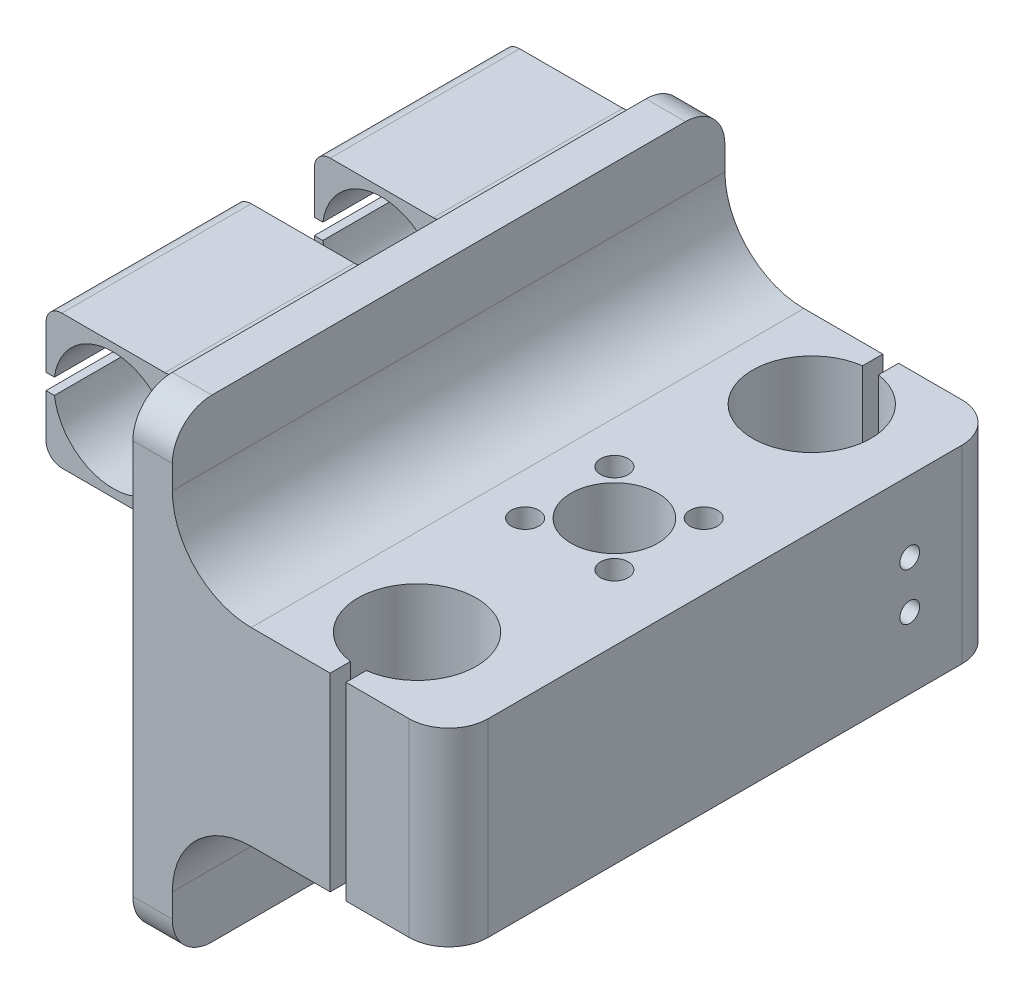
SolidWorks part; units mm, degrees
ref_plane "Plan de face" through (0, 0, 0) normal (0, 0, 1) x (1, 0, 0)
ref_plane "Plan de dessus" through (0, 0, 0) normal (0, 1, 0) x (1, 0, 0)
ref_plane "Plan de droite" through (0, 0, 0) normal (1, 0, 0) x (0, 0, -1)
sketch "Sketch1" plane through (0, 0, 0) normal (1, 0, 0) x (0, 0, -1)
  line L4 (-37.2098, 55.762) -> (32.7902, 55.762)
  line L7 (-37.2098, 55.762) -> (-37.2098, -4.238)
  line L8 (-37.2098, -4.238) -> (32.7902, -4.238)
  line L9 (32.7902, 55.762) -> (32.7902, -4.238)
  dimension "D1" = 70
  dimension "D2" = 60
extrude "Boss-Extrude3" add sketch "Sketch1" along normal blind 5
fillet "Fillet2" radius 5 4 edges at (2.5, -4.238, 37.2098) (2.5, -4.238, -32.7902) (2.5, 55.762, -32.7902) (2.5, 55.762, 37.2098)
sketch "Sketch4" plane through (5, 0, 0) normal (1, 0, 0) x (0, 0, -1)
  line L1 (-37.2098, 13.762) -> (32.7902, 13.762)
  line L2 (-37.2098, 13.762) -> (-37.2098, 37.762)
  line L3 (-37.2098, 37.762) -> (32.7902, 37.762)
  line L4 (32.7902, 13.762) -> (32.7902, 37.762)
  line L5 (32.7902, 0.762) -> (32.7902, 50.762) construction
  line L6 (-37.2098, 50.762) -> (-37.2098, 0.762) construction
  point P8 (32.7902, 25.762)
  point P9 (32.7902, 25.762)
  dimension "D1" = 24
extrude "Boss-Extrude5" add sketch "Sketch4" along normal blind 35
fillet "Fillet4" radius 5 2 edges at (40, 25.762, 37.2098) (40, 25.762, -32.7902)
sketch "Sketch5" plane through (0, 13.762, 0) normal (0, -1, 0) x (-1, 0, 0)
  line L0 (-47, -37.2098) -> (-47, 32.7902) construction
  line L1 (-35, -37.2098) -> (-5, -37.2098) construction
  line L2 (-35, 32.7902) -> (-5, 32.7902) construction
  line L4 (-5, -37.2098) -> (-5, 32.7902) construction
  line L5 (-47, -37.2098) -> (-5, 32.7902) construction
  line L6 (-47, 32.7902) -> (-5, -37.2098) construction
  line L7 (-20.3431, -2.2098) -> (-31.6569, -2.2098) construction
  line L8 (-31.6569, -7.8666) -> (-20.3431, -7.8666) construction
  line L9 (-31.6569, -7.8666) -> (-31.6569, 3.4471) construction
  line L10 (-31.6569, 3.4471) -> (-20.3431, 3.4471) construction
  line L11 (-20.3431, -7.8666) -> (-20.3431, 3.4471) construction
  line L12 (-31.6569, -7.8666) -> (-20.3431, 3.4471) construction
  line L13 (-31.6569, 3.4471) -> (-20.3431, -7.8666) construction
  line L14 (-26, -7.8666) -> (-26, 3.4471) construction
  line L15 (-27, 27.895) -> (-25, 27.895)
  line L16 (-27, 27.895) -> (-27, 37.3036)
  line L17 (-27, 37.3036) -> (-25, 37.3036)
  line L18 (-25, 27.895) -> (-25, 37.3036)
  line L19 (-27, -41.5182) -> (-25, -41.5182)
  line L20 (-27, -41.5182) -> (-27, -32.5795)
  line L21 (-27, -32.5795) -> (-25, -32.5795)
  line L22 (-25, -41.5182) -> (-25, -32.5795)
  circle A0 centre (-31.6569, 3.4471) radius 1.75
  circle A1 centre (-31.6569, -7.8666) radius 1.75
  circle A2 centre (-20.3431, -7.8666) radius 1.75
  circle A3 centre (-20.3431, 3.4471) radius 1.75
  circle A4 centre (-26, -2.2098) radius 5.5
  circle A5 centre (-26, 22.7902) radius 7.5
  circle A6 centre (-26, -27.2098) radius 7.5
  point P10 (-26, -2.2098)
  point P36 (-26, 27.895)
  point P37 (-26, -41.5182)
  line M32 (-35, -37.2098) -> (-5, -37.2098)
  line M34 (-5, 32.7902) -> (-35, 32.7902)
  dimension "D5" = 11
  dimension "D6" = 3.5
  dimension "D7" = 3.5
  dimension "D8" = 3.5
  dimension "D9" = 3.5
  dimension "D3" = 15
  dimension "D2" = 42
  dimension "D4" = 25
  dimension "D10" = 8
  dimension "D11" = 0
  dimension "D12" = 2
  dimension "D13" = 2
extrude "Cut-Extrude2" cut sketch "Sketch5" against normal through all both and the other way through all contours A6 | A5 | A1 | A0 | A3 | A2 | A4 | L18 A5 L16 L15 | A5 L18 L16 M34 | L18 L17 L16 M34 | A6 L22 L21 L20 | L22 A6 L20 M32 | L19 L22 L20 M32 region at (26, 13.762, -29.0816) region at (26, 13.762, -22.6166) region at (26, 13.762, -31.529) region at (26, 13.762, -35.0469) region at (26, 13.762, 39.364) region at (26, 13.762, 35.9486) region at (26, 13.762, 27.0528) region at (26, 13.762, 33.6336) region at (31.6569, 13.762, -3.4471) region at (31.6569, 13.762, 7.8666) region at (20.3431, 13.762, 7.8666) region at (20.3431, 13.762, -3.4471) region at (26, 13.762, 2.2098)
fillet "Fillet5" radius 10 2 edges at (5, 13.762, 2.2098) (5, 37.762, 2.2098)
sketch "Sketch6" plane through (0, 0, 0) normal (-1, 0, 0) x (0, 0, 1)
  line L0 (-9.7902, 14.262) -> (14.2098, 14.262)
  line L1 (-26.7902, 54.262) -> (-2.7902, 54.262)
  line L2 (-26.7902, 54.262) -> (-26.7902, 37.262)
  line L3 (-26.7902, 37.262) -> (-2.7902, 37.262)
  line L4 (-2.7902, 54.262) -> (-2.7902, 37.262)
  line L5 (-9.7902, 14.262) -> (-9.7902, -2.738)
  line L6 (-9.7902, -2.738) -> (14.2098, -2.738)
  line L7 (14.2098, 14.262) -> (14.2098, -2.738)
  line L8 (7.2098, 54.262) -> (31.2098, 54.262)
  line L9 (7.2098, 54.262) -> (7.2098, 37.262)
  line L10 (7.2098, 37.262) -> (31.2098, 37.262)
  line L11 (31.2098, 54.262) -> (31.2098, 37.262)
  line L12 (32.2098, -4.238) -> (-27.7902, -4.238) construction
  line L13 (-27.7902, 55.762) -> (32.2098, 55.762) construction
  point P16 (-9.7902, 5.762)
  point P17 (-26.7902, 45.762)
  point P18 (-2.7902, 45.762)
  point P19 (7.2098, 45.762)
  point P22 (2.2098, -2.738)
  point P25 (2.2098, -4.238)
  point P30 (2.2098, 55.762)
  dimension "D1" = 17
  dimension "D2" = 24
  dimension "D3" = 17
  dimension "D4" = 24
  dimension "D5" = 17
  dimension "D6" = 24
  dimension "D7" = 40
  dimension "D8" = 10
  dimension "D9" = 1.5
  dimension "D10" = 1.5
  dimension "D11" = 5
extrude "Boss-Extrude6" add sketch "Sketch6" along normal blind 17
sketch "Sketch7" plane through (0, 0, -26.7902) normal (0, 0, -1) x (-1, 0, 0)
  line L0 (17, 14.262) -> (0, 14.262) construction
  line L1 (17, 14.262) -> (17, -2.738) construction
  line L2 (17, 54.262) -> (0, 54.262) construction
  line L3 (17, 54.262) -> (17, 37.262) construction
  line L5 (14.7083, 46.762) -> (18.6764, 46.762)
  line L6 (14.7083, 46.762) -> (14.7083, 44.762)
  line L7 (14.7083, 44.762) -> (18.6764, 44.762)
  line L8 (18.6764, 46.762) -> (18.6764, 44.762)
  line L9 (14.795, 6.762) -> (19.3087, 6.762)
  line L10 (14.795, 6.762) -> (14.795, 4.762)
  line L11 (14.795, 4.762) -> (19.3087, 4.762)
  line L12 (19.3087, 6.762) -> (19.3087, 4.762)
  circle A0 centre (8.5, 45.762) radius 7.5
  circle A1 centre (8.5, 5.762) radius 7.5
  point P7 (8.5, 14.262)
  point P11 (17, 5.762)
  point P15 (8.5, 54.262)
  point P17 (14.7083, 45.762)
  point P20 (17, 45.762)
  point P25 (14.795, 5.762)
  line M5 (17, 37.262) -> (17, 54.262)
  dimension "D1" = 15
  dimension "D2" = 15
  dimension "D3" = 2
  dimension "D4" = 2
extrude "Cut-Extrude3" cut sketch "Sketch7" against normal through all both and the other way through all contours L5 A0 L7 L6 | L7 A0 L5 L6 | A0 L7 L5 M5 | L8 L5 L7 M5 | L9 A1 L11 L10 | L11 A1 L9 L10 | A1 L11 L12 L9 region at (-8.4003, 45.762, -26.7902) region at (-15.3432, 45.762, -26.7902) region at (-16.4887, 45.762, -26.7902) region at (-17.8382, 45.762, -26.7902) region at (-8.4066, 5.762, -26.7902) region at (-15.3865, 5.762, -26.7902) region at (-17.6432, 5.762, -26.7902)
fillet "Fillet6" radius 2 12 edges at (-17, -2.738, 2.2098) (-17, 14.262, 2.2098) (-17, 54.262, 19.2098) (-17, 37.262, 19.2098) (-17, 37.262, -14.7902) (-17, 54.262, -14.7902) (0, 54.262, -14.7902) (0, 54.262, 19.2098) (0, 14.262, 2.2098) (0, -2.738, 2.2098) (0, 37.262, -14.7902) (0, 37.262, 19.2098)
sketch "Sketch8" plane through (0, 14.262, 0) normal (0, 1, 0) x (1, 0, 0)
  line L0 (-15, 9.7902) -> (-2, 9.7902) construction
  line L1 (-3.5, 9.7902) -> (-13.5, 9.7902)
  line L2 (-3.5, 9.7902) -> (-3.5, 4.7902)
  line L3 (-3.5, 4.7902) -> (-13.5, 4.7902)
  line L4 (-13.5, 9.7902) -> (-13.5, 4.7902)
  line L5 (-15, -14.2098) -> (-2, -14.2098) construction
  line L6 (-3.5, -14.2098) -> (-13.5, -14.2098)
  line L7 (-3.5, -14.2098) -> (-3.5, -9.2098)
  line L8 (-3.5, -9.2098) -> (-13.5, -9.2098)
  line L9 (-13.5, -14.2098) -> (-13.5, -9.2098)
  point P15 (-8.5, 9.7902)
  point P16 (-8.5, 9.7902)
  dimension "D1" = 10
  dimension "D2" = 5
  dimension "D3" = 5
extrude "Boss-Extrude7" add sketch "Sketch8" along normal blind 10
sketch "Sketch9" plane through (0, 0, -9.7902) normal (0, 0, -1) x (-1, 0, 0)
  line L0 (3.5, 24.262) -> (13.5, 24.262) construction
  line L1 (5, 22.762) -> (12, 22.762)
  line L2 (5, 22.762) -> (5, 15.762)
  line L3 (5, 15.762) -> (12, 15.762)
  line L4 (12, 22.762) -> (12, 15.762)
  line L5 (3.5, 24.262) -> (3.5, 14.262) construction
  point P4 (8.5, 22.762)
  point P7 (8.5, 24.262)
  point P8 (5, 19.262)
  point P11 (3.5, 19.262)
  dimension "D1" = 7
  dimension "D2" = 7
extrude "Cut-Extrude4" cut sketch "Sketch9" against normal through all both and the other way through all
fillet "Fillet7" radius 1 4 edges at (-3.5, 24.262, 11.7098) (-13.5, 24.262, 11.7098) (-3.5, 24.262, -7.2902) (-13.5, 24.262, -7.2902)
sketch "Sketch10" plane through (5, 0, 0) normal (1, 0, 0) x (0, 0, -1)
  line L0 (-32.2098, -4.238) -> (27.7902, -4.238) construction
  line L1 (-12.0598, 10.762) -> (7.6402, 10.762)
  line L2 (-12.0598, 10.762) -> (-12.0598, -4.238)
  line L3 (-12.0598, -4.238) -> (7.6402, -4.238)
  line L4 (7.6402, 10.762) -> (7.6402, -4.238)
  circle A0 centre (-7.0598, 3.762) radius 1.15
  circle A1 centre (2.4402, 3.762) radius 1.15
  point P4 (-2.2098, -4.238)
  point P7 (-2.2098, -4.238)
  line M6 (32.7902, 3.762) -> (-37.2098, 3.762)
  line M9 (-32.2098, -4.238) -> (27.7902, -4.238)
  dimension "D3" = 2.3
  dimension "D4" = 2.3
  dimension "D1" = 19.7
  dimension "D2" = 15
  dimension "D5" = 9.5
  dimension "D6" = 8
  dimension "D7" = 5.2
extrude "Cut-Extrude5" cut sketch "Sketch10" along normal through all contours A1 L4 L1 L2 A0 M6 | A1 A0 L2 L4 M6 M9 | A0 M6 | A0 M6 | A1 M6 | A1 M6 region at (5, 7.3556, 2.2067) region at (5, -0.3331, 2.2071) region at (5, 3.274, 7.0598) region at (5, 4.2501, 7.0598) region at (5, 4.2501, -2.4402) region at (5, 3.274, -2.4402)
extrude "Cut-Extrude6" cut sketch "Sketch10<3>" against normal blind 3 contours A0 M6 | A0 M6 | A1 M6 | A1 M6 region at (5, 3.274, 7.0598) region at (5, 4.2501, 7.0598) region at (5, 4.2501, -2.4402) region at (5, 3.274, -2.4402)
sketch "Sketch10<3>" plane through (5, 0, 0) normal (1, 0, 0) x (0, 0, -1) same geometry as "Sketch10"
sketch "Sketch11" plane through (40, 0, 0) normal (1, 0, 0) x (0, 0, -1)
  line L0 (21.2, 28.762) -> (21.2, 22.762) construction
  line L1 (27.7902, 13.762) -> (27.7902, 37.762) construction
  circle A0 centre (21.2, 28.762) radius 1.25
  circle A1 centre (21.2, 22.762) radius 1.25
  point P5 (21.2, 25.762)
  point P8 (27.7902, 25.762)
  dimension "D1" = 2.5
  dimension "D2" = 2.5
  dimension "D3" = 6
extrude "Cut-Extrude7" cut sketch "Sketch11" against normal blind 3
